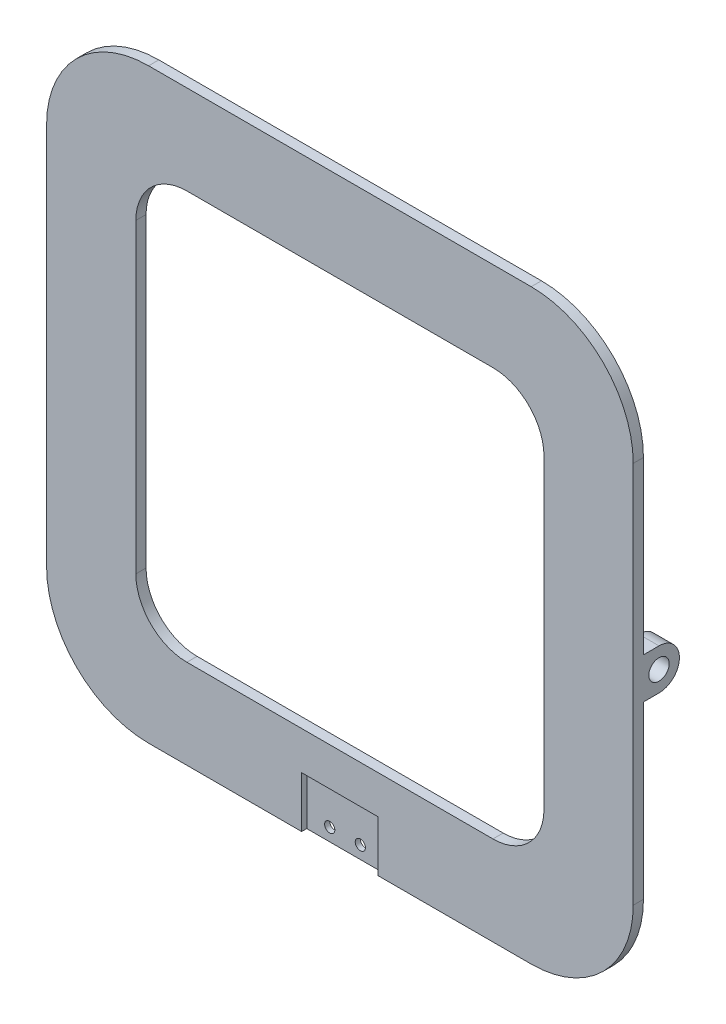
SolidWorks part; units mm, degrees
ref_plane "Płaszczyzna przednia" through (0, 0, 0) normal (0, 0, 1) x (1, 0, 0)
ref_plane "Płaszczyzna górna" through (0, 0, 0) normal (0, 1, 0) x (1, 0, 0)
ref_plane "Płaszczyzna prawa" through (0, 0, 0) normal (1, 0, 0) x (0, 0, -1)
sketch "Szkic1" plane through (0, 0, 0) normal (0, 0, 1) x (1, 0, 0)
  line L0 (0, -57.5) -> (115, -57.5) construction
  line L1 (0, 0) -> (115, 0)
  line L2 (0, 0) -> (0, -115)
  line L3 (0, -115) -> (115, -115)
  line L4 (115, 0) -> (115, -115)
  dimension "D1" = 115
  dimension "D2" = 115
extrude "Dodanie-wyciągnięcie1" add sketch "Szkic1" along normal blind 2
sketch "Szkic3" plane through (115, 0, 0) normal (1, 0, 0) x (0, 0, -1)
  line L0 (0, -115) -> (0, 0) construction
  line L1 (0, -53.5) -> (3.0506, -53.5)
  line L2 (0, -53.5) -> (0, -61.5)
  line L3 (0, -61.5) -> (3.0506, -61.5)
  line L6 (-2, -115) -> (0, -115) construction
  arc A0 (3.0506, -61.5) -> (3.0506, -53.5) centre (3.0506, -57.5) ccw
  dimension "D1" = 8
  dimension "D2" = 53.5
extrude "Dodanie-wyciągnięcie2" add sketch "Szkic3" against normal blind 4
ref_plane "Płaszczyzna1" through (57.5, 0, 0) normal (1, 0, 0) x (0, 0, -1)
mirror "Lustro1" about plane through (57.5, 0, 0) normal (1, 0, 0) of "Dodanie-wyciągnięcie2"
sketch "Szkic5" plane through (115, 0, 0) normal (1, 0, 0) x (0, 0, -1)
  circle A0 centre (3.0506, -57.5) radius 2
  arc A1 (3.0506, -61.5) -> (3.0506, -53.5) centre (3.0506, -57.5) ccw construction
  dimension "D1" = 4
extrude "Wytnij-wyciągnięcie1" cut sketch "Szkic5" against normal through all
sketch "Szkic6" plane through (0, 0, 2) normal (0, 0, 1) x (1, 0, 0)
  line L0 (0, 0) -> (0, -115) construction
  line L2 (0, -115) -> (115, -115) construction
  circle A0 centre (54.5, -112.5) radius 1
  circle A1 centre (60.5, -112.5) radius 1
  dimension "D1" = 2
  dimension "D2" = 2
  dimension "D5" = 2.5
  dimension "D6" = 2.5
  dimension "D3" = 6
  dimension "D4" = 54.5
extrude "Wytnij-wyciągnięcie2" cut sketch "Szkic6" against normal blind 10
fillet "Zaokrąglenie1" radius 20 4 edges at (0, -115, 1) (115, -115, 1) (0, 0, 1) (115, 0, 1)
sketch "Szkic7" plane through (0, 0, 2) normal (0, 0, 1) x (1, 0, 0)
  line L0 (20, -115) -> (95, -115) construction
  line L1 (50, -115) -> (65, -115)
  line L2 (50, -115) -> (50, -105)
  line L3 (50, -105) -> (65, -105)
  line L4 (65, -115) -> (65, -105)
  line L5 (0, -20) -> (0, -95) construction
  dimension "D1" = 10
  dimension "D2" = 15
  dimension "D3" = 50
extrude "Wytnij-wyciągnięcie3" cut sketch "Szkic7" against normal blind 1
sketch "Szkic8" plane through (0, 0, 0) normal (0, 0, -1) x (-1, 0, 0)
  line L0 (0, -20) -> (0, -53.5) construction
  line L1 (-87.5, -97.5) -> (-27.5, -97.5)
  line L2 (-97.5, -87.5) -> (-97.5, -27.5)
  line L3 (-87.5, -17.5) -> (-27.5, -17.5)
  line L4 (-17.5, -87.5) -> (-17.5, -27.5)
  line L5 (-97.5, -97.5) -> (-17.5, -17.5) construction
  line L6 (-97.5, -17.5) -> (-17.5, -97.5) construction
  line L7 (-95, 0) -> (-20, 0) construction
  arc A0 (-87.5, -97.5) -> (-97.5, -87.5) centre (-87.5, -87.5) cw
  arc A1 (-27.5, -97.5) -> (-17.5, -87.5) centre (-27.5, -87.5) ccw
  arc A2 (-27.5, -17.5) -> (-17.5, -27.5) centre (-27.5, -27.5) cw
  arc A3 (-97.5, -27.5) -> (-87.5, -17.5) centre (-87.5, -27.5) cw
  point P0 (-57.5, -57.5)
  dimension "D5" = 10
  dimension "D1" = 80
  dimension "D2" = 80
  dimension "D3" = 17.5
  dimension "D4" = 17.5
extrude "Wytnij-wyciągnięcie4" cut sketch "Szkic8" against normal blind 10
